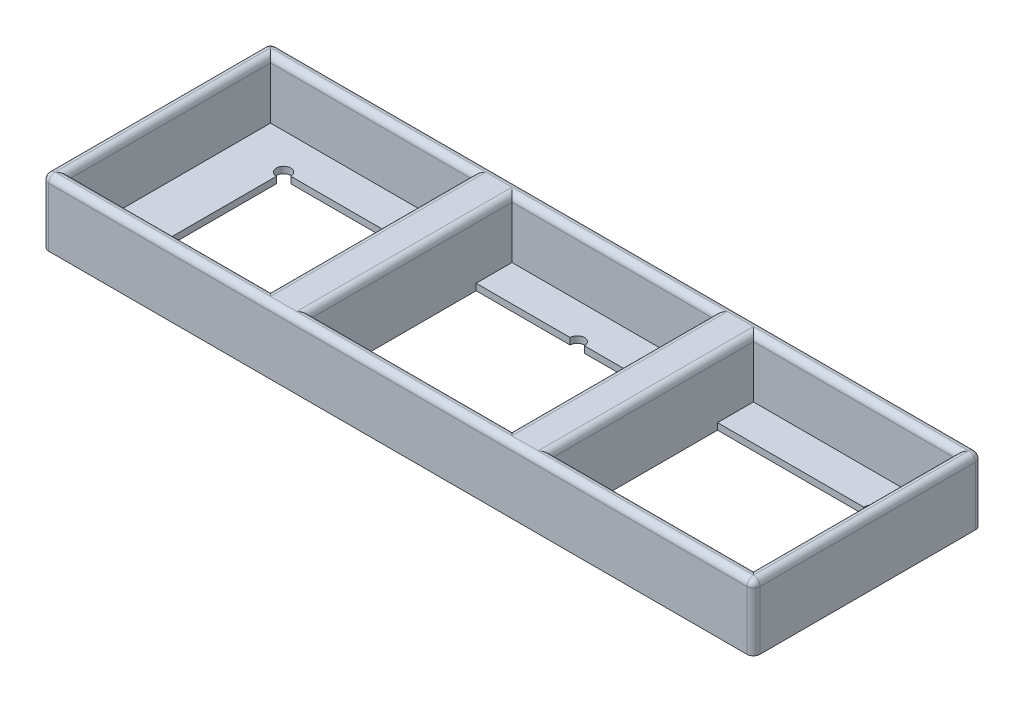
SolidWorks part; units mm, degrees
note: The reader was unsure of these and kept them because the rebuilt part matched: shared geometry of "草图1<3>".
ref_plane "前视基准面" through (0, 0, 0) normal (0, 0, 1) x (1, 0, 0)
ref_plane "上视基准面" through (0, 0, 0) normal (0, 1, 0) x (1, 0, 0)
ref_plane "右视基准面" through (0, 0, 0) normal (1, 0, 0) x (0, 0, -1)
sketch "草图1" plane through (0, 0, 0) normal (0, 1, 0) x (1, 0, 0)
  line L0 (-7, 7) -> (-7, -7) construction
  line L1 (30, 7) -> (44, 7) construction
  line L4 (30, 7) -> (30, -7) construction
  line L5 (30, -7) -> (44, -7) construction
  line L6 (44, 7) -> (44, -7) construction
  line L7 (37, -7) -> (37, 7) construction
  line L8 (30, 0) -> (44, 0) construction
  line L9 (-7, 7) -> (7, 7) construction
  line L10 (7, 7) -> (7, -7) construction
  line L11 (-7, -7) -> (7, -7) construction
  line L12 (-44, 7) -> (-44, -7) construction
  line L13 (-44, 7) -> (-30, 7) construction
  line L14 (-30, 7) -> (-30, -7) construction
  line L15 (-44, -7) -> (-30, -7) construction
  line L16 (30, 7) -> (-7, 7) construction
  line L17 (0, 7) -> (0, -7) construction
  line L18 (-50, 15) -> (50, 15) construction
  line L19 (-50, 15) -> (-50, -15) construction
  line L20 (-50, -15) -> (50, -15) construction
  line L21 (50, 15) -> (50, -15) construction
  line L22 (0, -15) -> (0, 15) construction
  line L23 (-50, 0) -> (50, 0) construction
  line L24 (-45, 10) -> (45, 10) construction
  line L25 (45, 10) -> (45, -10) construction
  line L26 (-45, -10) -> (45, -10) construction
  line L27 (-45, 10) -> (-45, -10) construction
  line L31 (-15, 15) -> (15, 15) construction
  line L32 (-15, 15) -> (-15, -15) construction
  line L33 (-15, -15) -> (15, -15) construction
  line L34 (15, 15) -> (15, -15) construction
  line L35 (0, -15) -> (0, 15) construction
  line L36 (-15, 0) -> (15, 0) construction
  line L44 (-44, 7) -> (-30, -7) construction
  line L45 (-21.5, 15.5) -> (-21.5, -15.5)
  line L46 (-52, 15) -> (-22, 15) construction
  line L47 (-52, 15) -> (-52, -15) construction
  line L48 (-52, -15) -> (-22, -15) construction
  line L49 (-22, 15) -> (-22, -15) construction
  line L50 (-37, -15) -> (-37, 15) construction
  line L51 (-52, 0) -> (-22, 0) construction
  line L52 (22, 15) -> (52, 15) construction
  line L53 (22, 15) -> (22, -15) construction
  line L54 (22, -15) -> (52, -15) construction
  line L55 (52, 15) -> (52, -15) construction
  line L56 (37, -15) -> (37, 15) construction
  line L57 (22, 0) -> (52, 0) construction
  line L58 (-52.5, 15.5) -> (52.5, 15.5)
  line L59 (-52.5, 15.5) -> (-52.5, -15.5)
  line L60 (-52.5, -15.5) -> (52.5, -15.5)
  line L61 (52.5, 15.5) -> (52.5, -15.5)
  line L62 (-15.5, 15.5) -> (-15.5, -15.5)
  line L63 (15.5, 15.5) -> (15.5, -15.5)
  line L64 (21.5, 15.5) -> (21.5, -15.5)
  line L66 (-45, 10) -> (45, 10)
  line L67 (-45, 10) -> (-45, -10)
  line L68 (-45, -10) -> (45, -10)
  line L69 (45, 10) -> (45, -10)
  line L70 (-21.5, -15.5) -> (-15.5, -15.5)
  line L71 (15.5, 15.5) -> (21.5, 15.5)
  line L72 (15.5, -15.5) -> (21.5, -15.5)
  line L73 (-54.5, 17.5) -> (54.5, 17.5)
  line L74 (54.5, 17.5) -> (54.5, -17.5)
  line L75 (-54.5, -17.5) -> (54.5, -17.5)
  line L76 (-54.5, 17.5) -> (-54.5, -17.5)
  circle A0 centre (-45, 10) radius 1.1
  circle A1 centre (-45, -10) radius 1.1
  circle A2 centre (45, 10) radius 1.1
  circle A3 centre (45, -10) radius 1.1
  circle A4 centre (0, -10) radius 1.1
  circle A5 centre (0, 10) radius 1.1
  point P0 (37, 0)
  point P1 (0, 0)
  point P17 (0, 0)
  point P18 (0, 0)
  point P31 (0, 10)
  point P32 (0, -10)
  point P58 (-37, 0)
  point P62 (37, 0)
  dimension "D6" = 2.2
  dimension "D7" = 2.2
  dimension "D8" = 2.2
  dimension "D9" = 2.2
  dimension "D10" = 2.2
  dimension "D11" = 2.2
  dimension "D1" = 14
  dimension "D2" = 14
  dimension "D3" = 37
  dimension "D4" = 100
  dimension "D5" = 30
  dimension "D12" = 14
  dimension "D13" = 23
  dimension "D14" = 23
  dimension "D15" = 5
  dimension "D16" = 5
  dimension "D17" = 5
  dimension "D18" = 5
  dimension "D19" = 3
  dimension "D20" = 1
  dimension "D21" = 3
  dimension "D22" = 3
  dimension "D23" = 30
  dimension "D26" = 30
  dimension "D27" = 30
  dimension "D24" = 0.5
  dimension "D25" = 0.5
  dimension "D28" = 0.5
  dimension "D29" = 0.5
  dimension "D30" = 0.5
  dimension "D31" = 0.5
  dimension "D32" = 0.5
  dimension "D33" = 0.5
  dimension "D34" = 2
extrude "凸台-拉伸1" add sketch "草图1" along normal blind 1 contours A1 L67 A0 L66 L45 L58 L59 L60 L68 | A4 L68 L62 L60 L63 | A5 L66 L63 L58 L62 | A3 L68 L64 L60 L61 L58 L66 A2 L69
extrude "凸台-拉伸2" add sketch "草图1<3>" along normal blind 10
sketch "草图1<3>" plane through (0, 0, 0) normal (0, 1, 0) x (1, 0, 0) same geometry as "草图1"
fillet "圆角1" radius 1 8 edges at (54.5, 10, 0) (0, 10, 17.5) (-54.5, 10, 0) (0, 10, -17.5) (54.5, 5, 17.5) (54.5, 5, -17.5) (-54.5, 5, -17.5) (-54.5, 5, 17.5)
fillet "圆角2" radius 1 12 edges at (21.5, 10, 0) (-37, 10, 15.5) (37, 10, 15.5) (-15.5, 10, 0) (-52.5, 10, 0) (0, 10, 15.5) (0, 10, -15.5) (15.5, 10, 0) (37, 10, -15.5) (52.5, 10, 0) (-37, 10, -15.5) (-21.5, 10, 0)
